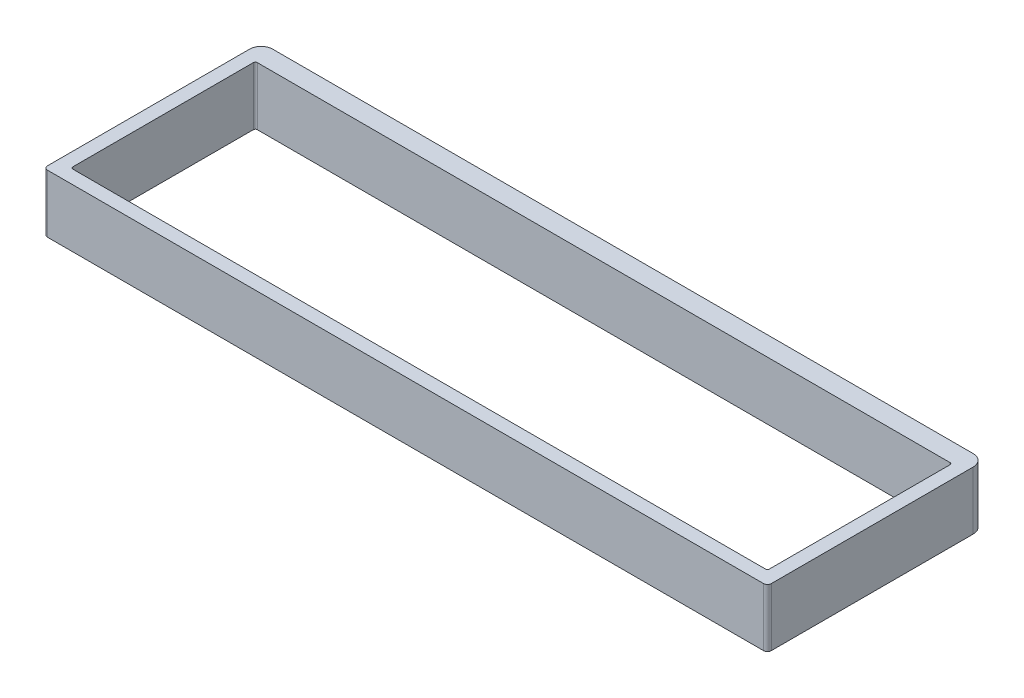
SolidWorks part; units mm, degrees
ref_plane "Front Plane" through (0, 0, 0) normal (0, 0, 1) x (1, 0, 0)
ref_plane "Top Plane" through (0, 0, 0) normal (0, 1, 0) x (1, 0, 0)
ref_plane "Right Plane" through (0, 0, 0) normal (1, 0, 0) x (0, 0, -1)
sketch "Sketch1" plane through (0, 0, 0) normal (0, 1, 0) x (1, 0, 0)
  line L1 (-178.825, 47.625) -> (178.825, 47.625)
  line L2 (-179.825, 46.625) -> (-179.825, -46.625)
  line L3 (-178.825, -47.625) -> (178.825, -47.625)
  line L4 (179.825, 46.625) -> (179.825, -46.625)
  line L5 (-179.825, 47.625) -> (179.825, -47.625) construction
  line L6 (-179.825, -47.625) -> (179.825, 47.625) construction
  arc A0 (178.825, -47.625) -> (179.825, -46.625) centre (178.825, -46.625) ccw
  arc A1 (178.825, 47.625) -> (179.825, 46.625) centre (178.825, 46.625) cw
  arc A2 (-179.825, -46.625) -> (-178.825, -47.625) centre (-178.825, -46.625) ccw
  arc A3 (-178.825, 47.625) -> (-179.825, 46.625) centre (-178.825, 46.625) ccw
  circle A4 centre (157.075, 19.175) radius 1.1
  circle A5 centre (136.925, -16.775) radius 1.1
  circle A6 centre (-153.475, 33.725) radius 1.1
  circle A7 centre (17.925, 22.275) radius 1.1
  circle A8 centre (17.875, -35.075) radius 1.1
  circle A9 centre (-130.375, -35.725) radius 1.1
  point P0 (0, 0)
  dimension "D3" = 1
  dimension "D4" = 2.2
  dimension "D7" = 2.2
  dimension "D8" = 2.2
  dimension "D9" = 2.2
  dimension "D10" = 2.2
  dimension "D11" = 2.2
  dimension "D1" = 359.65
  dimension "D2" = 95.25
  dimension "D5" = 22.75
  dimension "D6" = 28.45
  dimension "D12" = 42.9
  dimension "D13" = 30.85
  dimension "D14" = 25.35
  dimension "D15" = 161.9
  dimension "D16" = 12.55
  dimension "D17" = 161.95
  dimension "D18" = 11.9
  dimension "D19" = 49.45
  dimension "D20" = 13.9
  dimension "D21" = 26.35
sketch "Sketch2" plane through (0, 0, 0) normal (0, 1, 0) x (1, 0, 0)
  line L0 (-179.825, 46.625) -> (-179.825, -46.625) construction
  line L1 (-178.825, -47.625) -> (178.825, -47.625) construction
  line L2 (179.825, 46.625) -> (179.825, -46.625) construction
  line L3 (-178.825, 47.625) -> (178.825, 47.625) construction
  line L4 (-179.825, 46.625) -> (-179.825, -46.625)
  line L5 (-178.825, -47.625) -> (178.825, -47.625)
  line L6 (179.825, 46.625) -> (179.825, -46.625)
  line L7 (-178.825, 47.625) -> (178.825, 47.625)
  line L9 (-180.825, 57.625) -> (180.825, 57.625)
  line L10 (-186.825, 51.625) -> (-186.825, -52.625)
  line L11 (-184.825, -54.625) -> (184.825, -54.625)
  line L12 (186.825, 51.625) -> (186.825, -52.625)
  circle A0 centre (157.075, 19.175) radius 1.1 construction
  circle A1 centre (136.925, -16.775) radius 1.1 construction
  circle A2 centre (17.875, -35.075) radius 1.1 construction
  circle A3 centre (17.925, 22.275) radius 1.1 construction
  circle A4 centre (-153.475, 33.725) radius 1.1 construction
  circle A5 centre (-130.375, -35.725) radius 1.1 construction
  arc A6 (-179.825, -46.625) -> (-178.825, -47.625) centre (-178.825, -46.625) ccw construction
  arc A7 (178.825, -47.625) -> (179.825, -46.625) centre (178.825, -46.625) ccw construction
  arc A8 (179.825, 46.625) -> (178.825, 47.625) centre (178.825, 46.625) ccw construction
  arc A9 (-178.825, 47.625) -> (-179.825, 46.625) centre (-178.825, 46.625) ccw construction
  circle A10 centre (157.075, 19.175) radius 1.1
  circle A11 centre (136.925, -16.775) radius 1.1
  circle A12 centre (17.875, -35.075) radius 1.1
  circle A13 centre (17.925, 22.275) radius 1.1
  circle A14 centre (-153.475, 33.725) radius 1.1
  circle A15 centre (-130.375, -35.725) radius 1.1
  arc A16 (-179.825, -46.625) -> (-178.825, -47.625) centre (-178.825, -46.625) ccw
  arc A17 (178.825, -47.625) -> (179.825, -46.625) centre (178.825, -46.625) ccw
  arc A18 (179.825, 46.625) -> (178.825, 47.625) centre (178.825, 46.625) ccw
  arc A19 (-178.825, 47.625) -> (-179.825, 46.625) centre (-178.825, 46.625) ccw
  arc A20 (180.825, 57.625) -> (186.825, 51.625) centre (180.825, 51.625) cw
  arc A21 (-180.825, 57.625) -> (-186.825, 51.625) centre (-180.825, 51.625) ccw
  arc A22 (184.825, -54.625) -> (186.825, -52.625) centre (184.825, -52.625) ccw
  arc A23 (-186.825, -52.625) -> (-184.825, -54.625) centre (-184.825, -52.625) ccw
  point P30 (0, 0)
  dimension "D5" = 6
  dimension "D6" = 2
  dimension "D1" = 10
  dimension "D2" = 7
  dimension "D3" = 7
  dimension "D4" = 7
extrude "Boss-Extrude1" add sketch "Sketch2" along normal blind 30 contours L10 A23 L11 A22 L12 A20 L9 A21 A19 L7 A18 L6 A17 L5 A16 L4 region at (0, 0, -53.7235)
sketch "Sketch4" plane through (0, 0, 0) normal (0, -1, 0) x (1, 0, 0)
  line L4 (-179.825, 46.625) -> (-179.825, -46.625)
  line L5 (178.825, 47.625) -> (-178.825, 47.625)
  line L6 (179.825, -46.625) -> (179.825, 46.625)
  line L7 (-178.825, -47.625) -> (178.825, -47.625)
  line L8 (-179.825, 46.625) -> (-179.825, -46.625)
  line L9 (178.825, 47.625) -> (-178.825, 47.625)
  line L10 (179.825, -46.625) -> (179.825, 46.625)
  line L11 (-178.825, -47.625) -> (178.825, -47.625)
  arc A4 (-179.825, -46.625) -> (-178.825, -47.625) centre (-178.825, -46.625) ccw
  arc A5 (-178.825, 47.625) -> (-179.825, 46.625) centre (-178.825, 46.625) ccw
  arc A6 (179.825, 46.625) -> (178.825, 47.625) centre (178.825, 46.625) ccw
  arc A7 (178.825, -47.625) -> (179.825, -46.625) centre (178.825, -46.625) ccw
  arc A8 (-179.825, -46.625) -> (-178.825, -47.625) centre (-178.825, -46.625) ccw
  arc A9 (-178.825, 47.625) -> (-179.825, 46.625) centre (-178.825, 46.625) ccw
  arc A10 (179.825, 46.625) -> (178.825, 47.625) centre (178.825, 46.625) ccw
  arc A11 (178.825, -47.625) -> (179.825, -46.625) centre (178.825, -46.625) ccw
  dimension "D1" = 0
